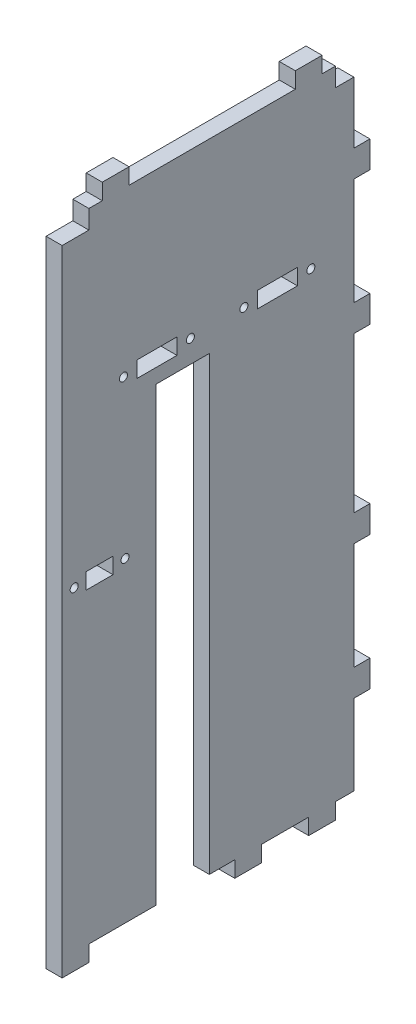
SolidWorks part; units mm, degrees
ref_plane "Plan de face" through (0, 0, 0) normal (0, 0, 1) x (1, 0, 0)
ref_plane "Plan de dessus" through (0, 0, 0) normal (0, 1, 0) x (1, 0, 0)
ref_plane "Plan de droite" through (0, 0, 0) normal (1, 0, 0) x (0, 0, -1)
sketch "Esquisse1" plane through (0, 0, 0) normal (1, 0, 0) x (0, 0, -1)
  line L0 (97.1531, 0) -> (-102.2664, 0) construction
  line L1 (-54.5, 119) -> (54.5, 119)
  line L2 (-54.5, 119) -> (-54.5, -119)
  line L3 (-54.5, -119) -> (54.5, -119)
  line L4 (54.5, 119) -> (54.5, -119)
  line L5 (0, 172.7153) -> (0, -236.1933) construction
  line L7 (-45.5, 2) -> (-35.5, 2)
  line L8 (-45.5, 2) -> (-45.5, -4)
  line L9 (-45.5, -4) -> (-35.5, -4)
  line L10 (-35.5, 2) -> (-35.5, -4)
  line L15 (-26.585, 61) -> (-11.585, 61)
  line L16 (-26.585, 61) -> (-26.585, 55)
  line L17 (-26.585, 55) -> (-11.585, 55)
  line L18 (-11.585, 61) -> (-11.585, 55)
  line L19 (18.415, 61) -> (33.415, 61)
  line L20 (18.415, 61) -> (18.415, 55)
  line L21 (18.415, 55) -> (33.415, 55)
  line L22 (33.415, 61) -> (33.415, 55)
  dimension "D1" = 238
  dimension "D2" = 109
  dimension "D4" = 119
  dimension "D13" = 15
  dimension "D14" = 15
  dimension "D15" = 30
  dimension "D16" = 6
  dimension "D17" = 6
  dimension "D3" = 54.5
  dimension "D5" = 58
  dimension "D6" = 27.915
  dimension "D7" = 9
  dimension "D8" = 117
  dimension "D9" = 6
  dimension "D10" = 10
extrude "Boss.-Extru.1" add sketch "Esquisse1" along normal blind 6
sketch "Esquisse3" plane through (6, 0, 0) normal (1, 0, 0) x (0, 0, -1)
  line L0 (-54.5, -119) -> (54.5, -119) construction
  line L1 (-54.5, -119) -> (-44.5, -119)
  line L2 (-54.5, -119) -> (-54.5, -125)
  line L3 (-54.5, -125) -> (-44.5, -125)
  line L4 (-44.5, -119) -> (-44.5, -125)
  line L5 (245.3741, 0) -> (-166.5298, 0) construction
  line L6 (54.5, -119) -> (54.5, 119) construction
  line L7 (37.62, -119) -> (47.62, -119)
  line L8 (37.62, -119) -> (37.62, -125)
  line L9 (37.62, -125) -> (47.62, -125)
  line L10 (0, 208.6671) -> (0, -232.3841) construction
  line L11 (-54.5, -119) -> (54.5, -119) construction
  line L12 (47.62, -119) -> (47.62, -125)
  line L13 (60.5, 39) -> (60.5, 29)
  line L14 (54.5, 29) -> (60.5, 29)
  line L15 (54.5, 39) -> (54.5, 29)
  line L16 (54.5, 39) -> (60.5, 39)
  line L17 (60.5, 89) -> (60.5, 79)
  line L18 (54.5, 79) -> (60.5, 79)
  line L19 (54.5, 89) -> (54.5, 79)
  line L20 (54.5, 89) -> (60.5, 89)
  line L21 (54.5, 119) -> (-54.5, 119) construction
  line L22 (54.5, -89) -> (60.5, -89)
  line L23 (54.5, -89) -> (54.5, -79)
  line L24 (54.5, -79) -> (60.5, -79)
  line L25 (60.5, -89) -> (60.5, -79)
  line L26 (54.5, -39) -> (60.5, -39)
  line L27 (54.5, -39) -> (54.5, -29)
  line L28 (54.5, -29) -> (60.5, -29)
  line L29 (0, -208.6671) -> (0, 232.3841) construction
  line L30 (10, -119) -> (20, -119)
  line L31 (10, -119) -> (10, -125)
  line L32 (10, -125) -> (20, -125)
  line L33 (20, -119) -> (20, -125)
  line L34 (54.5, -119) -> (54.5, 119) construction
  line L35 (60.5, -39) -> (60.5, -29)
  line L36 (42.62, 119) -> (32.62, 119)
  line L37 (42.62, 119) -> (42.62, 125)
  line L38 (42.62, 125) -> (32.62, 125)
  line L39 (32.62, 119) -> (32.62, 125)
  line L40 (-54.5, 119) -> (-54.5, -119) construction
  line L41 (-29.5, 119) -> (-39.5, 119)
  line L42 (-29.5, 119) -> (-29.5, 125)
  line L43 (-29.5, 125) -> (-39.5, 125)
  line L44 (-39.5, 119) -> (-39.5, 125)
  dimension "D2" = 10
  dimension "D3" = 6
  dimension "D4" = 10
  dimension "D5" = 6.88
  dimension "D6" = 6
  dimension "D7" = 6
  dimension "D8" = 10
  dimension "D9" = 6
  dimension "D10" = 10
  dimension "D11" = 6
  dimension "D12" = 10
  dimension "D13" = 17.62
  dimension "D14" = 30
  dimension "D15" = 40
  dimension "D16" = 6
  dimension "D17" = 10
  dimension "D18" = 11.88
  dimension "D19" = 15
  dimension "D20" = 10
  dimension "D21" = 6
extrude "Boss.-Extru.5" add sketch "Esquisse3" against normal blind 6
sketch "Esquisse6" plane through (6, 0, 0) normal (1, 0, 0) x (0, 0, -1)
  line L0 (-44.5, -119) -> (10, -119) construction
  line L1 (-19.5, -119) -> (0.5, -119)
  line L2 (-19.5, -119) -> (-19.5, 49.59)
  line L3 (-19.5, 49.59) -> (0.5, 49.59)
  line L4 (0.5, -119) -> (0.5, 49.59)
  line L5 (54.5, -79) -> (54.5, -39) construction
  line L8 (32.62, 119) -> (-29.5, 119) construction
  dimension "D1" = 20
  dimension "D2" = 69.41
  dimension "D3" = 54
extrude "Enlèv. mat.-Extru.2" cut sketch "Esquisse6" against normal blind 6
sketch "Esquisse7" plane through (0, 0, 0) normal (-1, 0, 0) x (0, 0, 1)
  line L1 (-54.5, 119) -> (-47.62, 119)
  line L2 (-54.5, 119) -> (-54.5, 112)
  line L3 (-54.5, 112) -> (-47.62, 112)
  line L4 (-47.62, 119) -> (-47.62, 112)
  dimension "D1" = 7
  dimension "D2" = 6.88
extrude "Enlèv. mat.-Extru.3" cut sketch "Esquisse7" against normal blind 6
sketch "Esquisse8" plane through (0, 0, 0) normal (-1, 0, 0) x (0, 0, 1)
  line L0 (-51.0214, 58) -> (44.3386, 58) construction
  line L1 (-33.415, 55) -> (-33.415, 61) construction
  line L2 (-18.415, 61) -> (-18.415, 55) construction
  line L3 (11.585, 55) -> (11.585, 61) construction
  line L4 (26.585, 61) -> (26.585, 55) construction
  line L5 (60.5401, -1) -> (10.4957, -1) construction
  line L6 (45.5, 2) -> (45.5, -4) construction
  line L7 (35.5, -4) -> (35.5, 2) construction
  circle A0 centre (-38.415, 58) radius 1.5
  circle A1 centre (-13.415, 58) radius 1.5
  circle A2 centre (6.585, 58) radius 1.5
  circle A3 centre (31.585, 58) radius 1.5
  circle A4 centre (31, -1) radius 1.5
  circle A5 centre (50, -1) radius 1.5
  dimension "D1" = 3
  dimension "D2" = 3
  dimension "D3" = 3
  dimension "D4" = 3
  dimension "D5" = 5
  dimension "D6" = 5
  dimension "D7" = 5
  dimension "D8" = 5
  dimension "D9" = 3
  dimension "D10" = 3
  dimension "D11" = 4.5
  dimension "D12" = 4.5
extrude "Enlèv. mat.-Extru.4" cut sketch "Esquisse8" against normal blind 6
sketch "Esquisse9" plane through (0, 0, 0) normal (-1, 0, 0) x (0, 0, 1)
  line L1 (54.5, 119) -> (44.5, 119)
  line L2 (54.5, 119) -> (54.5, 112)
  line L3 (54.5, 112) -> (44.5, 112)
  line L4 (44.5, 119) -> (44.5, 112)
  dimension "D1" = 10
  dimension "D2" = 7
extrude "Enlèv. mat.-Extru.5" cut sketch "Esquisse9" against normal blind 6
equation "\"D3@Esquisse1\"=\"D2@Esquisse1\"/2"
equation "\"D4@Esquisse1\"=\"D1@Esquisse1\"/2"
